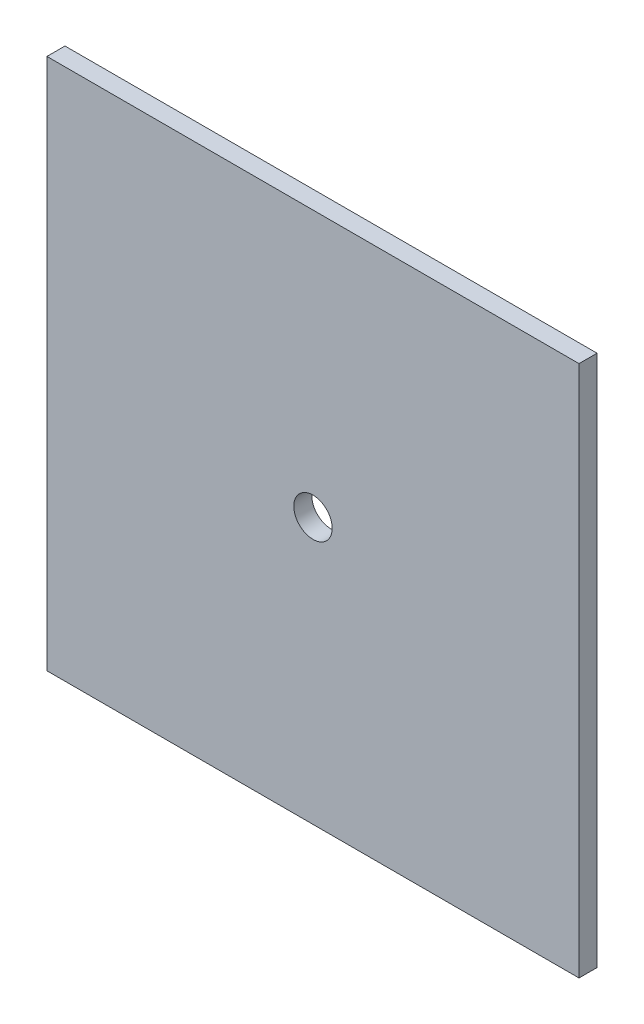
SolidWorks part; units mm, degrees
material "6061 Alloy"
ref_plane "Front Plane" through (0, 0, 0) normal (0, 0, 1) x (1, 0, 0)
ref_plane "Top Plane" through (0, 0, 0) normal (0, 1, 0) x (1, 0, 0)
ref_plane "Right Plane" through (0, 0, 0) normal (1, 0, 0) x (0, 0, -1)
sketch "Sketch1" plane through (0, 0, 0) normal (0, 0, 1) x (1, 0, 0)
  line L1 (-46.825, -46.825) -> (46.825, -46.825)
  line L2 (-46.825, -46.825) -> (-46.825, 46.825)
  line L3 (-46.825, 46.825) -> (46.825, 46.825)
  line L4 (46.825, -46.825) -> (46.825, 46.825)
  line L5 (-46.825, -46.825) -> (46.825, 46.825) construction
  line L6 (-46.825, 46.825) -> (46.825, -46.825) construction
  point P0 (0, 0)
  dimension "D1" = 93.65
  dimension "D2" = 93.65
extrude "Boss-Extrude1" add sketch "Sketch1" along normal blind 3.175
sketch "Sketch2" plane through (0, 0, 3.175) normal (0, 0, 1) x (1, 0, 0)
  point P0 (0, 0)
hole_wizard "1/4 Clearance Hole1" positions "Sketch2" profile "Sketch3" hole size "1/4" standard "ANSI Inch"
sketch "Sketch3" plane through (0, 0, 3.175) normal (1, 0, 0) x (0, -1, 0)
  line L0 (0, 0) -> (0, 6.8558)
  line L1 (0, 6.8558) -> (3.3782, 4.826)
  line L2 (3.3782, 4.826) -> (3.3782, 0)
  line L5 (3.3782, 0) -> (0, 0)
  line L10 (0, 6.8558) -> (-3.3782, 4.826) construction
  line L11 (0, -6.35) -> (0, 107.95) construction
  dimension "Hole Dia." = 6.7564
  dimension "Hole Depth" = 4.826
  dimension "Drill Angle" = 118
equation "\"side\"= 100mm"
equation "\"thk\"= 1 / 8"
equation "\"D1@Sketch1\"=\"side\"-(2*\"thk\")"
equation "\"D2@Sketch1\"=\"side\"-(2*\"thk\")"
equation "\"D1@Boss-Extrude1\"=\"thk\""
